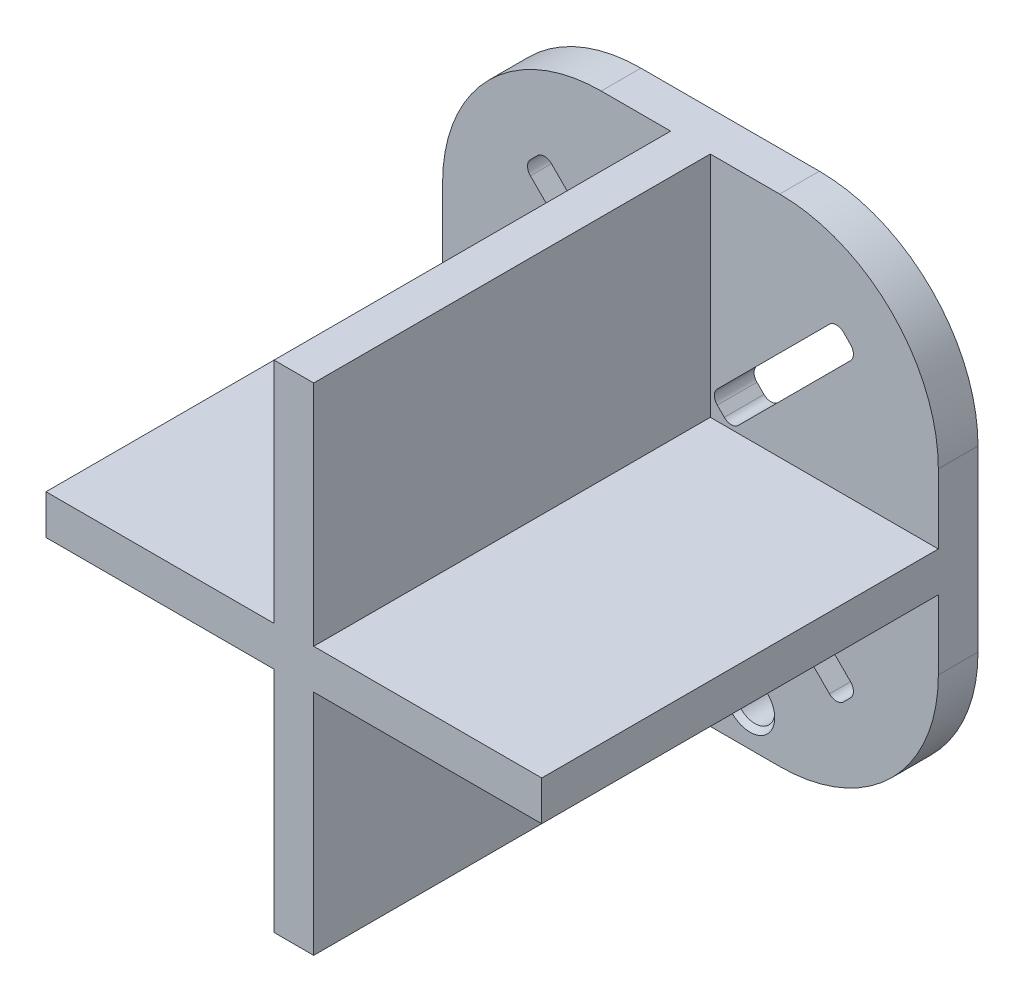
SolidWorks part; units mm, degrees
ref_plane "Płaszczyzna przednia" through (0, 0, 0) normal (0, 0, 1) x (1, 0, 0)
ref_plane "Płaszczyzna górna" through (0, 0, 0) normal (0, 1, 0) x (1, 0, 0)
ref_plane "Płaszczyzna prawa" through (0, 0, 0) normal (1, 0, 0) x (0, 0, -1)
sketch "Szkic2" plane through (0, 0, 0) normal (0, 0, 1) x (1, 0, 0)
  line L1 (0, 0) -> (25, 0)
  line L2 (0, 0) -> (0, -25)
  line L3 (0, -25) -> (25, -25)
  line L4 (25, 0) -> (25, -25)
  dimension "D1" = 25
  dimension "D2" = 25
extrude "Dodanie-wyciągnięcie1" add sketch "Szkic2" along normal blind 2
sketch "Szkic3" plane through (0, 0, 2) normal (0, 0, 1) x (1, 0, 0)
  line L0 (12.5, 0) -> (12.5, -25) construction
  line L2 (0, -25) -> (25, -25) construction
  line L3 (25, -25) -> (25, 0) construction
  line L4 (11.5, 0) -> (13.5, 0)
  line L5 (11.5, 0) -> (11.5, -11.5)
  line L6 (11.5, -25) -> (13.5, -25)
  line L7 (13.5, 0) -> (13.5, -11.5)
  line L8 (11.5, 0) -> (13.5, -25) construction
  line L9 (11.5, -25) -> (13.5, 0) construction
  line L10 (0, -11.5) -> (11.5, -11.5)
  line L11 (0, -11.5) -> (0, -13.5)
  line L12 (0, -13.5) -> (11.5, -13.5)
  line L13 (25, -11.5) -> (25, -13.5)
  line L14 (12.5, -12.5) -> (25, -13.5) construction
  line L15 (12.5, -12.5) -> (25, -11.5) construction
  line L17 (11.5, -13.5) -> (11.5, -25)
  line L18 (13.5, -13.5) -> (25, -13.5)
  line L19 (13.5, -11.5) -> (25, -11.5)
  line L20 (13.5, -13.5) -> (13.5, -25)
  point P6 (12.5, -12.5)
  point P12 (12.5, -12.5)
  dimension "D1" = 2
  dimension "D2" = 2
extrude "Dodanie-wyciągnięcie2" add sketch "Szkic3" along normal blind 20
fillet "Zaokrąglenie1" radius 8 4 edges at (25, -25, 1) (0, -25, 1) (25, 0, 1) (0, 0, 1)
sketch "Szkic7" plane through (0, 0, 2) normal (0, 0, 1) x (1, 0, 0)
  line L0 (10.4393, -13.5) -> (11.5, -14.5607)
  line L1 (10.4393, -13.5) -> (4.0754, -19.864)
  line L2 (11.5, -14.5607) -> (5.136, -20.9246)
  line L3 (4.0754, -19.864) -> (5.136, -20.9246)
  line L4 (10.4393, -13.5) -> (5.136, -20.9246) construction
  line L5 (11.5, -14.5607) -> (4.0754, -19.864) construction
  line L6 (0, -13.5) -> (11.5, -13.5) construction
  line L7 (11.5, -13.5) -> (11.5, -25) construction
  point P6 (7.7877, -17.2123)
  dimension "D1" = 45
  dimension "D2" = 1.5
  dimension "D3" = 9
extrude "Wytnij-wyciągnięcie1" cut sketch "Szkic7" against normal blind 20
fillet "Zaokrąglenie2" radius 0.5 4 edges at (5.136, -20.9246, 1) (4.0754, -19.864, 1) (11.5, -14.5607, 1) (10.4393, -13.5, 1)
sketch "Szkic9" plane through (0, 0, 2) normal (0, 0, 1) x (1, 0, 0)
  line L0 (11.5, -10.4393) -> (10.4393, -11.5)
  line L1 (11.5, -10.4393) -> (5.136, -4.0754)
  line L2 (10.4393, -11.5) -> (4.0754, -5.136)
  line L3 (5.136, -4.0754) -> (4.0754, -5.136)
  line L4 (11.5, -10.4393) -> (4.0754, -5.136) construction
  line L5 (10.4393, -11.5) -> (5.136, -4.0754) construction
  line L6 (11.5, 0) -> (11.5, -11.5) construction
  line L7 (11.5, -11.5) -> (0, -11.5) construction
  point P6 (7.7877, -7.7877)
  dimension "D1" = 1.5
  dimension "D2" = 45
  dimension "D3" = 9
extrude "Wytnij-wyciągnięcie2" cut sketch "Szkic9" against normal blind 20
sketch "Szkic11" plane through (0, 0, 2) normal (0, 0, 1) x (1, 0, 0)
  line L0 (13.5, -10.4393) -> (14.5607, -11.5)
  line L1 (13.5, -10.4393) -> (19.864, -4.0754)
  line L2 (14.5607, -11.5) -> (20.9246, -5.136)
  line L3 (19.864, -4.0754) -> (20.9246, -5.136)
  line L4 (13.5, -10.4393) -> (20.9246, -5.136) construction
  line L5 (14.5607, -11.5) -> (19.864, -4.0754) construction
  line L6 (13.5, -11.5) -> (13.5, 0) construction
  line L7 (25, -11.5) -> (13.5, -11.5) construction
  point P6 (17.2123, -7.7877)
  dimension "D1" = 45
  dimension "D2" = 1.5
  dimension "D3" = 9
extrude "Wytnij-wyciągnięcie3" cut sketch "Szkic11" against normal blind 20
sketch "Szkic12" plane through (0, 0, 2) normal (0, 0, 1) x (1, 0, 0)
  line L0 (14.5607, -13.5) -> (13.5, -14.5607)
  line L1 (14.5607, -13.5) -> (20.9246, -19.864)
  line L2 (13.5, -14.5607) -> (19.864, -20.9246)
  line L3 (20.9246, -19.864) -> (19.864, -20.9246)
  line L4 (14.5607, -13.5) -> (19.864, -20.9246) construction
  line L5 (13.5, -14.5607) -> (20.9246, -19.864) construction
  line L6 (13.5, -13.5) -> (25, -13.5) construction
  line L7 (13.5, -25) -> (13.5, -13.5) construction
  point P6 (17.2123, -17.2123)
  dimension "D1" = 9
  dimension "D2" = 1.5
  dimension "D3" = 45
extrude "Wytnij-wyciągnięcie4" cut sketch "Szkic12" against normal blind 20
fillet "Zaokrąglenie3" radius 0.5 12 edges at (4.0754, -5.136, 1) (5.136, -4.0754, 1) (11.5, -10.4393, 1) (10.4393, -11.5, 1) (19.864, -20.9246, 1) (20.9246, -19.864, 1) (20.9246, -5.136, 1) (19.864, -4.0754, 1) (14.5607, -11.5, 1) (13.5, -10.4393, 1) (13.5, -14.5607, 1) (14.5607, -13.5, 1)
sketch "Szkic13" plane through (0, 0, 2) normal (0, 0, 1) x (1, 0, 0)
  line L0 (11.5, -13.5) -> (11.5, -25) construction
  line L1 (8, -25) -> (11.5, -25) construction
  line L2 (13.5, -25) -> (13.5, -14.5607) construction
  line L3 (13.5, -25) -> (17, -25) construction
  circle A0 centre (9.5, -23) radius 1
  circle A1 centre (15.5, -23) radius 1
  dimension "D1" = 2
  dimension "D2" = 2
  dimension "D3" = 2
  dimension "D4" = 2
  dimension "D5" = 2
  dimension "D6" = 2
extrude "Wytnij-wyciągnięcie5" cut sketch "Szkic13" against normal blind 20
chamfer "Sfazowanie1" distance 0.25 angle 45 2 edges at (16.5, -23, 2) (10.5, -23, 2)
